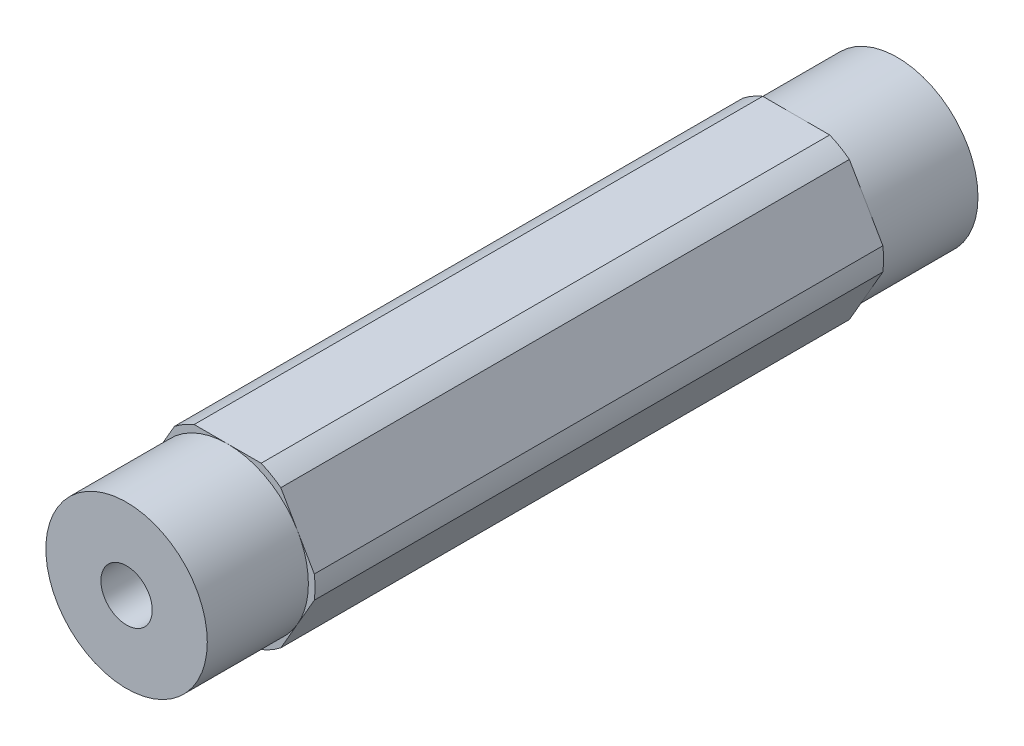
SolidWorks part; units mm, degrees
ref_plane "Front Plane" through (0, 0, 0) normal (0, 0, 1) x (1, 0, 0)
ref_plane "Top Plane" through (0, 0, 0) normal (0, 1, 0) x (1, 0, 0)
ref_plane "Right Plane" through (0, 0, 0) normal (1, 0, 0) x (0, 0, -1)
sketch "Sketch1" plane through (0, 0, 0) normal (0, 0, 1) x (1, 0, 0)
  line L1 (7.3323, 0) -> (3.6662, 6.35)
  line L2 (3.6662, 6.35) -> (-3.6662, 6.35)
  line L3 (-3.6662, 6.35) -> (-7.3323, 0)
  line L4 (-7.3323, 0) -> (-3.6662, -6.35)
  line L5 (-3.6662, -6.35) -> (3.6662, -6.35)
  line L6 (3.6662, -6.35) -> (7.3323, 0)
  circle A1 centre (0, 0) radius 6.35 construction
  dimension "D1" = 12.7
extrude "Boss-Extrude1" add sketch "Sketch1" along normal mid plane 60.6222 contours L3 L4 L5 L6 L1 L2
sketch "Sketch2" plane through (0, 0, 30.3111) normal (0, 0, 1) x (1, 0, 0)
  circle A0 centre (0, 0) radius 6.35
extrude "Cut-Extrude2" cut sketch "Sketch2" against normal blind 7.9502 flip side to cut
sketch "Sketch3" plane through (0, 0, 30.3111) normal (0, 0, 1) x (1, 0, 0)
  circle A0 centre (0, 0) radius 6.875
  dimension "D1" = 13.75
extrude "Cut-Extrude4" cut sketch "Sketch3" against normal through all flip side to cut
mirror "Mirror1" about plane through (0, 0, 0) normal (0, 0, 1) of "Cut-Extrude2"
sketch "Sketch4" plane through (0, 0, 30.3111) normal (0, 0, 1) x (1, 0, 0)
  circle A0 centre (0, 0) radius 2.0193
  dimension "D1" = 4.0386
extrude "Cut-Extrude5" cut sketch "Sketch4" against normal through all
equation "\"D1@Boss-Extrude1\"=1.75670+(2*(1/4))+(2*1/16)+0.005"
